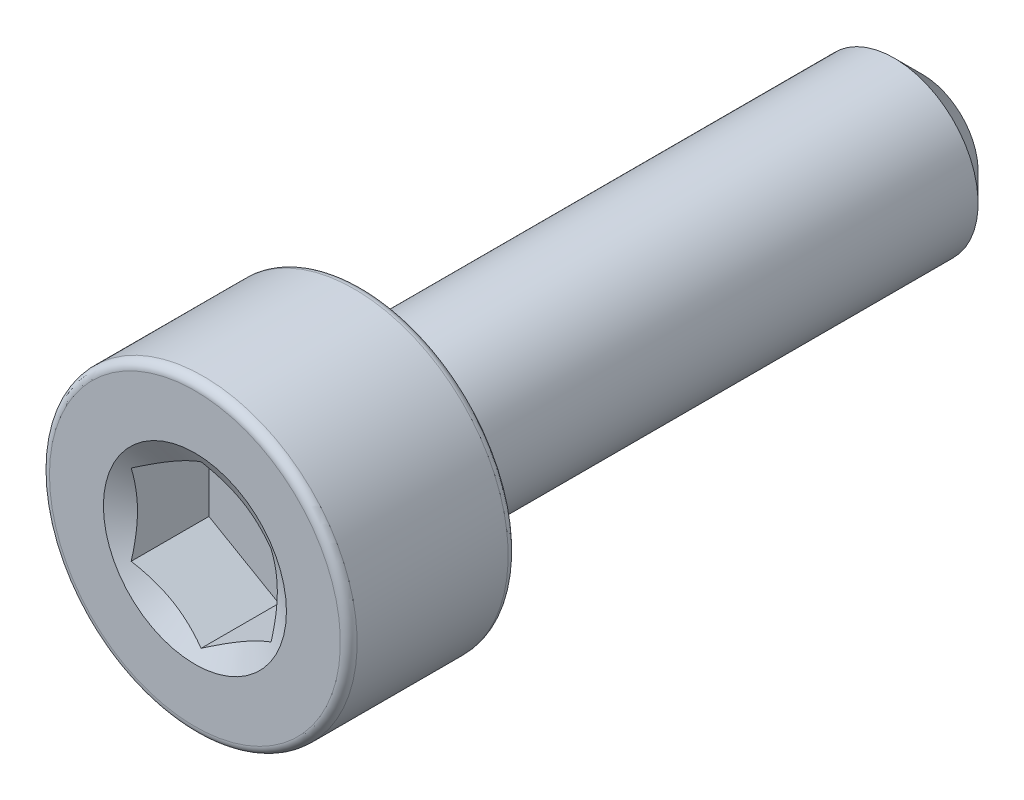
SolidWorks part; units mm, degrees
ref_plane "Front Plane" through (0, 0, 0) normal (0, 0, 1) x (1, 0, 0)
ref_plane "Top Plane" through (0, 0, 0) normal (0, 1, 0) x (1, 0, 0)
ref_plane "Right Plane" through (0, 0, 0) normal (1, 0, 0) x (0, 0, -1)
sketch "Sketch1" plane through (0, 0, 0) normal (1, 0, 0) x (0, 0, -1)
  line L0 (6.5, 0) -> (-6.5, 0) construction
  line L1 (-3.5, 2.75) -> (-3.5, -2.75) construction
  line L2 (6.5, 1.5) -> (6.5, -1.5) construction
  line L3 (6.4688, 1.5541) -> (6.7188, 1.1211) construction
  line L4 (6.6875, 1.1752) -> (6.75, 1.1752) construction
  line L5 (6.7188, 1.1211) -> (6.9688, 1.5541) construction
  line L6 (6.9688, 1.5541) -> (6.4688, 1.5541) construction
  line L7 (6.7188, 1.1752) -> (6.7188, 1.1211) construction
  line L8 (6.7188, 1.5541) -> (6.7188, 1.5) construction
  line L9 (6.9375, 1.5) -> (6.5, 1.5) construction
  point P4 (-3.5, 0)
  point P6 (-3.5, 1.25)
  point P7 (5.25, -1.5)
  point P20 (6.7188, 1.5271)
  dimension "Head Height" = 3
  dimension "Head Diameter" = 5.5
  dimension "Drive Size" = 2.5
  dimension "Length" = 10
  dimension "Thread Size" = 3
  dimension "Thread Pitch" = 0.5
  dimension "Pitch/8" = 0.0625
  dimension "Thread Note" = 1.25
sketch "Sketch2" plane through (0, 0, 0) normal (1, 0, 0) x (0, 0, -1)
  line L0 (6.5, 0) -> (6.5, 1)
  line L1 (6.5, 1.5) -> (6.5, -1.5) construction
  line L2 (6.5, 1) -> (6, 1.5)
  line L3 (6, 1.5) -> (-3.5, 1.5)
  line L4 (-3.5, 1.5) -> (-3.5, 2.6)
  line L5 (-3.65, 2.75) -> (-6.35, 2.75)
  line L6 (-6.5, 2.6) -> (-6.5, 0)
  line L7 (6.5, 0) -> (-6.5, 0) construction
  line L8 (-6.5, 0) -> (6.5, 0)
  arc A0 (-3.5, 2.6) -> (-3.65, 2.75) centre (-3.65, 2.6) ccw
  arc A1 (-6.35, 2.75) -> (-6.5, 2.6) centre (-6.35, 2.6) ccw
  point P19 (-3.5, 2.75)
  dimension "D3" = 0.15
  dimension "D1" = 0.5
  dimension "D2" = 45
revolve "Revolve1" add sketch "Sketch2" angle 360 about L0
sketch "Sketch3" plane through (0, 0, 0) normal (0, 0, 1) x (1, 0, 0)
  line L1 (-1.25, 0.7217) -> (-1.25, -0.7217)
  line L2 (-1.25, -0.7217) -> (0, -1.4434)
  line L3 (0, -1.4434) -> (1.25, -0.7217)
  line L4 (1.25, -0.7217) -> (1.25, 0.7217)
  line L5 (1.25, 0.7217) -> (0, 1.4434)
  line L6 (0, 1.4434) -> (-1.25, 0.7217)
  circle A0 centre (0, 0) radius 1.25 construction
  circle A1 centre (0, 0) radius 2.75 construction
extrude "Cut-Extrude1" cut sketch "Sketch3" against normal blind 1.5 from vertex starting at point (0, 0, 6.5)
sketch "Sketch4" plane through (0, 0, 6.5) normal (0, 0, 1) x (1, 0, 0)
  line L0 (0, 1.4434) -> (0, 1.8289) construction
  line L1 (0, 1.8289) -> (0, 2.2145) construction
  line L2 (0, 2.2145) -> (0, 2.6) construction
  circle A0 centre (0, 0) radius 1.6361
  point P12 (0, 1.6361)
extrude "Cut-Extrude2" cut sketch "Sketch4" against normal through all draft 60
split "Split1" [suppressed] bodies to split 106 112
sketch "Sketch5" [suppressed] plane through (0, 0, 0) normal (1, 0, 0) x (0, 0, -1)
  line L0 (6.6875, 1.1752) -> (6.75, 1.1752)
  line L1 (6.75, 1.1752) -> (6.9531, 1.5271)
  line L2 (6.9531, 1.5271) -> (6.4844, 1.5271)
  line L3 (6.4844, 1.5271) -> (6.6875, 1.1752)
  line L4 (6.4688, 1.5541) -> (6.7188, 1.1211) construction
sketch "Sketch6" [suppressed] plane through (0, 0, -6.5) normal (0, 0, -1) x (-1, 0, 0)
  circle A0 centre (0, 0) radius 1.5
curve "Helix/Spiral1" [suppressed] pitch 0.5 height 10.5 turns 21
sweep "Cut-Sweep1" [suppressed] cut profiles "Sketch5" path "Helix/Spiral1"
sketch "Sketch7" [suppressed] plane through (0, 0, 3.5) normal (0, 0, -1) x (-1, 0, 0)
  circle A0 centre (0, 0) radius 1.5508
  circle A1 centre (0, 0) radius 1.5 construction
  dimension "D1" = 0.0508
extrude "Boss-Extrude1" [suppressed] add sketch "Sketch7" along normal blind 1.5 draft 20 and the other way blind 0.3
equation "\"Pitch/8@Sketch1\" = \"Thread Pitch@Sketch1\" / 8"
equation "\"Thread Note@Sketch1\" = \"Thread Pitch@Sketch1\" * 2.5"
equation "\"D1@Sketch2\" = \"Thread Pitch@Sketch1\""
equation "\"D3@Sketch2\"=\"Head Height@Sketch1\"*.05"
equation "\"D1@Cut-Extrude1\" = \"Head Height@Sketch1\" * .5"
equation "\"D3@Helix/Spiral1\" = \"Length@Sketch1\" + \"Thread Pitch@Sketch1\""
equation "\"D4@Helix/Spiral1\" = \"Thread Pitch@Sketch1\""
equation "\"D2@Boss-Extrude1\" = \"Head Height@Sketch1\" * .1"
equation "\"D1\"= \"Thread Size@Sketch1\" * .4"
equation "\"D1@Boss-Extrude1\" = \"Thread Pitch@Sketch1\" * 3"
